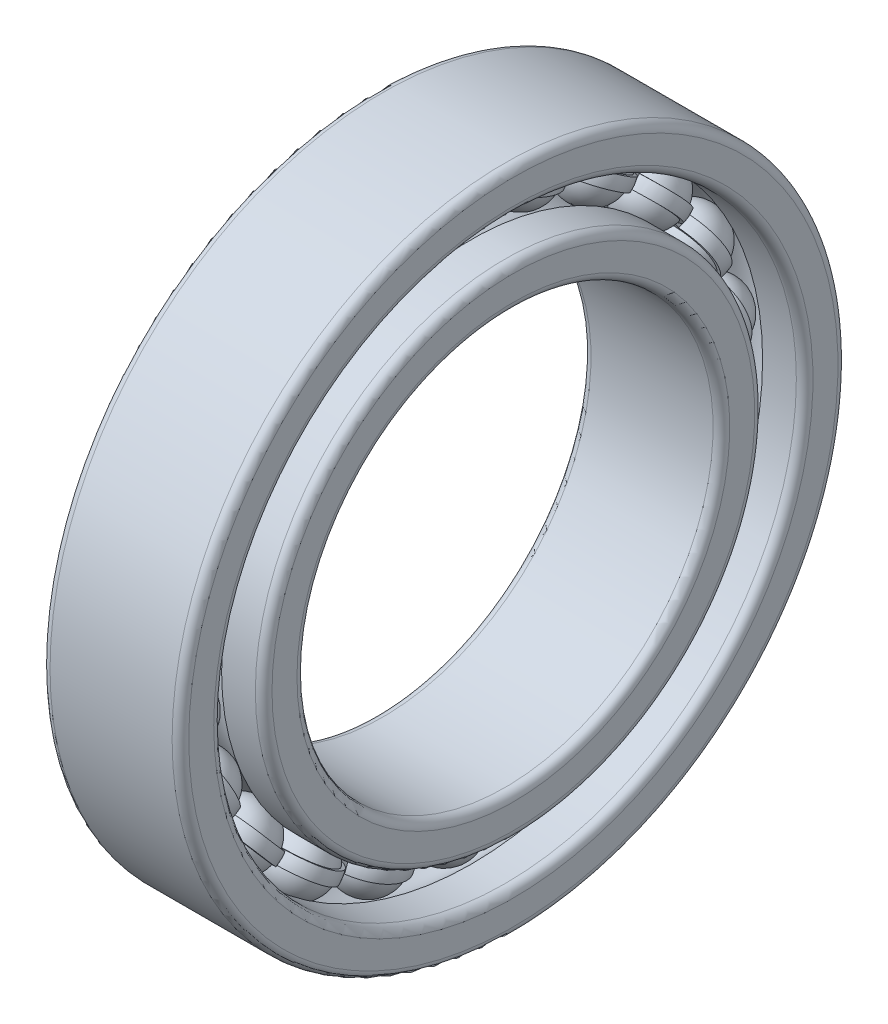
SolidWorks part; units mm, degrees
material "AISI 304"
ref_plane "前视基准面" through (0, 0, 0) normal (0, 0, 1) x (1, 0, 0)
ref_plane "上视基准面" through (0, 0, 0) normal (0, 1, 0) x (1, 0, 0)
ref_plane "右视基准面" through (0, 0, 0) normal (1, 0, 0) x (0, 0, -1)
sketch "尺寸草图" plane through (0, 0, 0) normal (0, 0, 1) x (1, 0, 0)
  line L0 (-19.9271, 0) -> (19.9271, 0) construction
  line L1 (0, 21.603) -> (0, -21.603) construction
  line L2 (-2.2, 12) -> (2.2, 12)
  line L3 (2.5, 11.7) -> (2.5, 10.8)
  line L4 (-2.5, 11.7) -> (-2.5, 10.8)
  line L5 (-2.2, 10.5) -> (2.2, 10.5)
  line L6 (-3.5, 9.75) -> (3.3577, 9.75) construction
  line L7 (-2.2, 9) -> (2.2, 9)
  line L8 (2.5, 8.7) -> (2.5, 7.8)
  line L9 (2.2, 7.5) -> (-2.2, 7.5)
  line L10 (-2.5, 7.8) -> (-2.5, 8.7)
  line L11 (0, 9.75) -> (0, 10.875) construction
  circle A0 centre (0, 9.75) radius 1.125
  arc A1 (2.5, 10.8) -> (2.2, 10.5) centre (2.2, 10.8) cw
  arc A2 (2.5, 8.7) -> (2.2, 9) centre (2.2, 8.7) ccw
  arc A3 (-2.2, 9) -> (-2.5, 8.7) centre (-2.2, 8.7) ccw
  arc A4 (-2.2, 10.5) -> (-2.5, 10.8) centre (-2.2, 10.8) cw
  arc A5 (-2.2, 7.5) -> (-2.5, 7.8) centre (-2.2, 7.8) cw
  arc A6 (2.2, 7.5) -> (2.5, 7.8) centre (2.2, 7.8) ccw
  arc A7 (2.5, 11.7) -> (2.2, 12) centre (2.2, 11.7) ccw
  arc A8 (-2.2, 12) -> (-2.5, 11.7) centre (-2.2, 11.7) ccw
  point P7 (0, 0)
  point P25 (-2.5, 9)
  point P28 (-2.5, 10.5)
  point P31 (-2.5, 7.5)
  point P36 (2.5, 12)
  point P39 (-2.5, 12)
  dimension "D1" = 0.375
  dimension "D3" = 0.3
  dimension "B" = 5
  dimension "D2" = 2.5
  dimension "D" = 24
  dimension "(d)" = 15
  dimension "D5" = 9.75
  dimension "D6" = 1.5
  dimension "D7" = 1.5
sketch "草图2" plane through (0, 0, 0) normal (0, 0, 1) x (1, 0, 0)
  line L6 (2.2, 7.5) -> (-2.2, 7.5) construction
  line L8 (-2.5, 11.7) -> (-2.5, 10.8) construction
  line L9 (-2.2, 10.5) -> (2.2, 10.5) construction
  line L10 (-2.2, 12) -> (2.2, 12) construction
  line L11 (2.5, 11.7) -> (2.5, 10.8) construction
  line L12 (2.5, 8.7) -> (2.5, 7.8) construction
  line L13 (-2.2, 9) -> (2.2, 9) construction
  line L14 (2.2, 7.5) -> (-2.2, 7.5)
  line L15 (-2.5, 7.8) -> (-2.5, 8.7) construction
  line L18 (-3.5, 0) -> (3.5, 0) construction
  line L19 (-19.9271, 0) -> (19.9271, 0) construction
  line L20 (-2.5, 11.7) -> (-2.5, 10.8)
  line L21 (-2.2, 10.5) -> (-0.8385, 10.5)
  line L22 (-2.2, 12) -> (2.2, 12)
  line L23 (2.5, 11.7) -> (2.5, 10.8)
  line L24 (2.5, 8.7) -> (2.5, 7.8)
  line L25 (-2.2, 9) -> (-0.8385, 9)
  line L26 (-2.5, 7.8) -> (-2.5, 8.7)
  line L27 (0.8385, 10.5) -> (2.2, 10.5)
  line L28 (0.8385, 9) -> (2.2, 9)
  circle A0 centre (0, 9.75) radius 1.125 construction
  arc A1 (0.8385, 10.5) -> (-0.8385, 10.5) centre (0, 9.75) ccw
  arc A2 (-0.8385, 9) -> (0.8385, 9) centre (0, 9.75) ccw
  arc A3 (-2.2, 12) -> (-2.5, 11.7) centre (-2.2, 11.7) ccw construction
  arc A4 (-2.5, 10.8) -> (-2.2, 10.5) centre (-2.2, 10.8) ccw construction
  arc A5 (2.5, 11.7) -> (2.2, 12) centre (2.2, 11.7) ccw construction
  arc A6 (2.2, 10.5) -> (2.5, 10.8) centre (2.2, 10.8) ccw construction
  arc A7 (2.5, 8.7) -> (2.2, 9) centre (2.2, 8.7) ccw construction
  arc A8 (2.2, 7.5) -> (2.5, 7.8) centre (2.2, 7.8) ccw construction
  arc A9 (-2.2, 9) -> (-2.5, 8.7) centre (-2.2, 8.7) ccw construction
  arc A10 (-2.5, 7.8) -> (-2.2, 7.5) centre (-2.2, 7.8) ccw construction
  arc A11 (-2.2, 12) -> (-2.5, 11.7) centre (-2.2, 11.7) ccw
  arc A12 (-2.5, 10.8) -> (-2.2, 10.5) centre (-2.2, 10.8) ccw
  arc A13 (2.5, 11.7) -> (2.2, 12) centre (2.2, 11.7) ccw
  arc A14 (2.2, 10.5) -> (2.5, 10.8) centre (2.2, 10.8) ccw
  arc A15 (2.5, 8.7) -> (2.2, 9) centre (2.2, 8.7) ccw
  arc A16 (2.2, 7.5) -> (2.5, 7.8) centre (2.2, 7.8) ccw
  arc A17 (-2.2, 9) -> (-2.5, 8.7) centre (-2.2, 8.7) ccw
  arc A18 (-2.5, 7.8) -> (-2.2, 7.5) centre (-2.2, 7.8) ccw
revolve "旋转1" add sketch "草图2" angle 360 about L18
sketch "草图5" plane through (0, 0, 0) normal (0, 0, 1) x (1, 0, 0)
  line L1 (-0.3375, 9.525) -> (0.3375, 9.525)
  line L2 (-0.3375, 9.525) -> (-0.3375, 9.975)
  line L3 (-0.3375, 9.975) -> (0.3375, 9.975)
  line L4 (0.3375, 9.525) -> (0.3375, 9.975)
  line L5 (-0.3375, 9.525) -> (0.3375, 9.975) construction
  line L6 (-0.3375, 9.975) -> (0.3375, 9.525) construction
  circle A0 centre (0, 9.75) radius 1.125 construction
  circle A1 centre (0, 9.75) radius 1.125 construction
  point P0 (0, 9.75)
  dimension "D1" = 0.675
  dimension "D2" = 0.45
revolve "旋转3" add sketch "草图5" angle 360 about L0
ref_axis "基准轴1" through (-3.85, 0, 0) along (1, 0, 0)
sketch "草图3" plane through (0, 0, 0) normal (0, 0, 1) x (1, 0, 0)
  line L1 (-1.2375, 9.75) -> (1.2375, 9.75)
  circle A0 centre (0, 9.75) radius 1.125 construction
  circle A1 centre (0, 9.75) radius 1.125 construction
  arc A2 (1.2375, 9.75) -> (-1.2375, 9.75) centre (0, 9.75) ccw
  dimension "D2" = 2.475
revolve "旋转2" add sketch "草图3" angle 360 about L1 region at (0, 10.2752, 0)
pattern_circular "阵列(圆周)5" count 22 over 360 about axis through (-3.85, 0, 0) along (1, 0, 0) of bodies 103
sketch "草图6" plane through (0, 0, 0) normal (0, 0, 1) x (1, 0, 0)
  line L0 (-1.2169, 9.975) -> (1.2169, 9.975)
  line L1 (-3.5, 9.75) -> (2.5, 9.75) construction
  line L3 (-1.2169, 9.525) -> (1.2169, 9.525)
  line L4 (2.5, -11.7) -> (2.5, 11.7) construction
  arc A0 (-1.2169, 9.525) -> (1.2169, 9.525) centre (0, 9.75) ccw
  circle A1 centre (0, 9.75) radius 1.125 construction
  circle A2 centre (0, 9.75) radius 1.125 construction
  arc A3 (1.2169, 9.975) -> (-1.2169, 9.975) centre (0, 9.75) ccw
  dimension "D1" = 2.475
  dimension "D3" = 0.225
  dimension "D4" = 0.225
revolve "切除-旋转1" cut sketch "草图6" angle 360 about L0
sketch "草图7" plane through (0, 0, 0) normal (0, 0, 1) x (1, 0, 0)
  line L0 (-1.125, 9.75) -> (1.125, 9.75)
  line L1 (-2.5, 0) -> (2.5, 0) construction
  line L2 (-2.5, 11.7) -> (-2.5, -11.7) construction
  line L3 (2.5, -11.7) -> (2.5, 11.7) construction
  circle A0 centre (0, 9.75) radius 1.125 construction
  arc A1 (1.125, 9.75) -> (-1.125, 9.75) centre (0, 9.75) ccw
revolve "旋转4" add sketch "草图7" angle 360 about L0
pattern_circular "阵列(圆周)2" count 22 over 360 about axis through (-3.85, 0, 0) along (1, 0, 0) of "旋转4"
